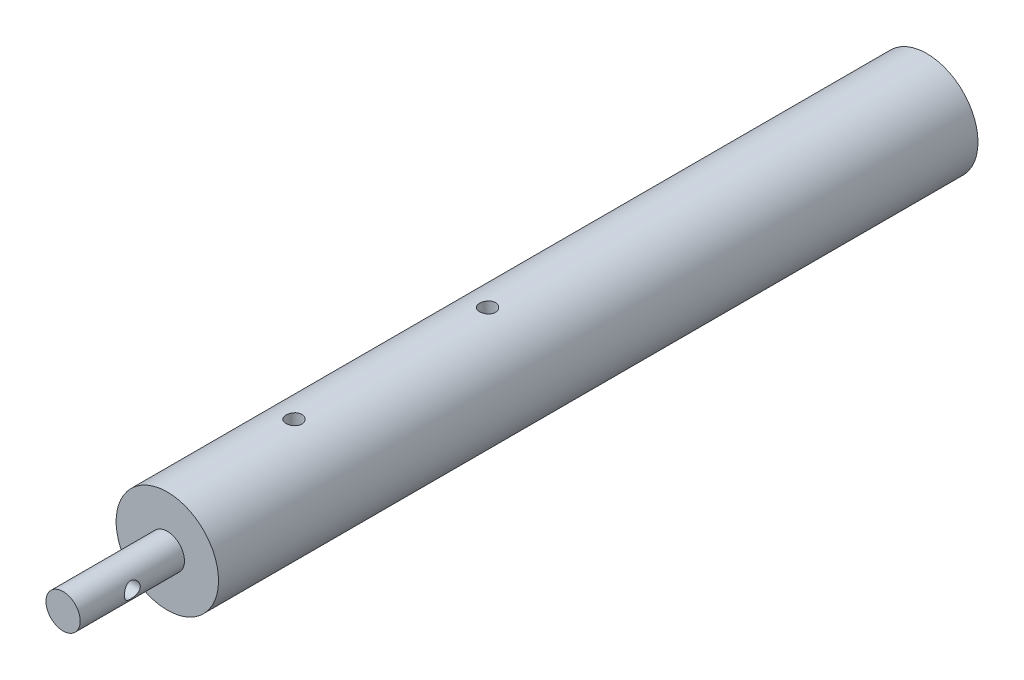
SolidWorks part; units mm, degrees
ref_plane "Front Plane" through (0, 0, 0) normal (0, 0, 1) x (1, 0, 0)
ref_plane "Top Plane" through (0, 0, 0) normal (0, 1, 0) x (1, 0, 0)
ref_plane "Right Plane" through (0, 0, 0) normal (1, 0, 0) x (0, 0, -1)
sketch "Sketch1" plane through (0, 0, 0) normal (0, 0, 1) x (1, 0, 0)
  circle A0 centre (0, 0) radius 8.7312
  dimension "D1" = 17.4625
extrude "Boss-Extrude1" add sketch "Sketch1" along normal blind 129.54
sketch "Sketch2" plane through (0, 0, 129.54) normal (0, 0, 1) x (1, 0, 0)
  circle A0 centre (0, 0) radius 2.921
  dimension "D1" = 5.842
extrude "Boss-Extrude2" add sketch "Sketch2" along normal blind 17.78
ref_plane "Plane1" through (0, 8.7312, 0) normal (0, 1, 0) x (1, 0, 0)
sketch "Sketch4" plane through (0, 8.7312, 0) normal (0, 1, 0) x (1, 0, 0)
  line L1 (-2.921, -147.32) -> (2.921, -147.32) construction
  circle A0 centre (0, -74.93) radius 1.8415
  circle A1 centre (0, -107.95) radius 1.8415
  dimension "D1" = 3.683
  dimension "D2" = 33.02
  dimension "D3" = 39.37
hole_wizard "#6-32 Tapped Hole1" positions "Sketch5" profile "Sketch6" tap size "#6-32" standard "ANSI Inch" end condition through all
sketch "Sketch5" plane through (0, 8.7312, 0) normal (0, 1, 0) x (1, 0, 0)
  point P0 (0, -74.93)
  point P3 (0, -107.95)
sketch "Sketch6" plane through (0, 8.7312, 74.93) normal (1, 0, 0) x (0, 0, 1)
  line L0 (0, 0) -> (0, 17.4625)
  line L1 (0, 17.4625) -> (1.3525, 17.4625)
  line L2 (1.3525, 17.4625) -> (1.3525, 0)
  line L5 (1.3525, 0) -> (0, 0)
  line L11 (0, -6.35) -> (0, 107.95) construction
  dimension "Thru Tap Drill Dia." = 2.7051
  dimension "Thru Tap Drill Depth" = 17.4625
cosmetic thread "Hole Thread1" parameters "D2"=3.5052
cosmetic thread "Hole Thread2" parameters "D2"=3.5052
ref_plane "Plane2" through (2.921, 0, 0) normal (1, 0, 0) x (0, 0, -1)
sketch "Sketch7" plane through (2.921, 0, 0) normal (1, 0, 0) x (0, 0, -1)
  line L1 (-147.32, 2.921) -> (-147.32, -2.921) construction
  circle A0 centre (-138.43, 0) radius 1.8415
  dimension "D1" = 3.683
  dimension "D2" = 8.89
hole_wizard "#6-32 Tapped Hole2" positions "Sketch8" profile "Sketch9" tap size "#6-32" standard "ANSI Inch" end condition through all
sketch "Sketch8" plane through (2.921, 0, 0) normal (1, 0, 0) x (0, 0, -1)
  point P0 (-138.43, 0)
sketch "Sketch9" plane through (2.921, 0, 138.43) normal (0, 1, 0) x (0, 0, -1)
  line L0 (0, 0) -> (0, 11.6522)
  line L1 (0, 11.6522) -> (1.3525, 11.6522)
  line L2 (1.3525, 11.6522) -> (1.3525, 0)
  line L5 (1.3525, 0) -> (0, 0)
  line L11 (0, -6.35) -> (0, 107.95) construction
  dimension "Thru Tap Drill Dia." = 2.7051
  dimension "Thru Tap Drill Depth" = 11.6522
cosmetic thread "Hole Thread3" parameters "D2"=3.5052
